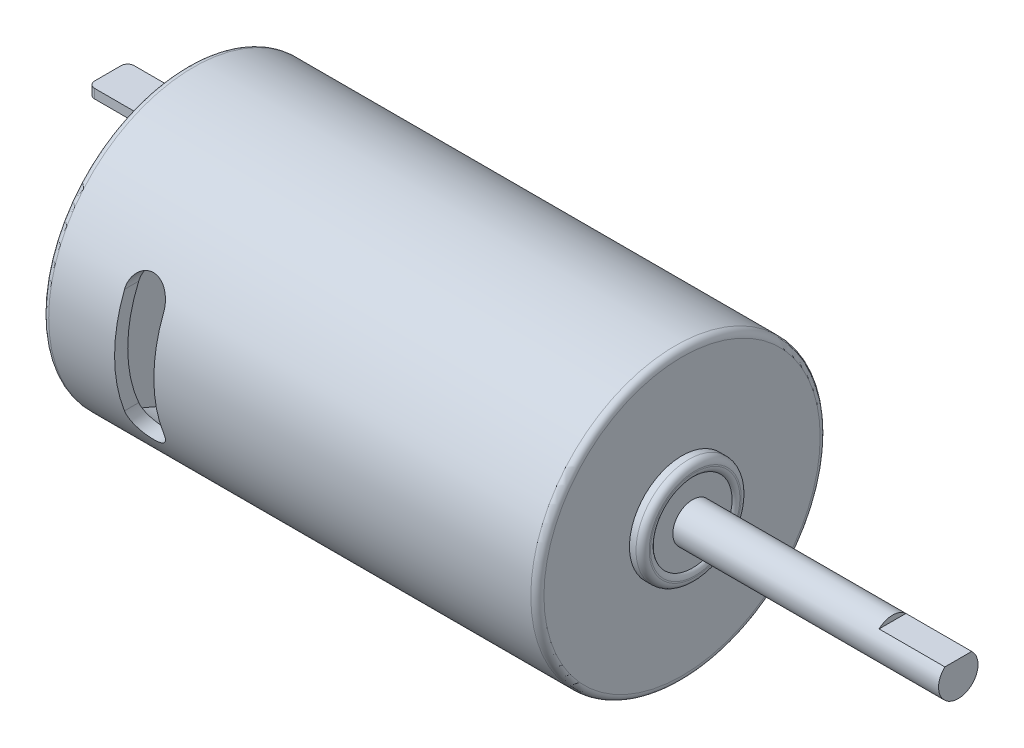
SolidWorks part; units mm, degrees
ref_plane "前视基准面" through (0, 0, 0) normal (0, 0, 1) x (1, 0, 0)
ref_plane "上视基准面" through (0, 0, 0) normal (0, 1, 0) x (1, 0, 0)
ref_plane "右视基准面" through (0, 0, 0) normal (1, 0, 0) x (0, 0, -1)
sketch "草图1" plane through (0, 0, 0) normal (1, 0, 0) x (0, 0, -1)
  circle A0 centre (0, 0) radius 11
  dimension "D1" = 22
extrude "凸台-拉伸1" add sketch "草图1" along normal mid plane 37.65
sketch "草图3" plane through (0, 0, 0) normal (1, 0, 0) x (0, 0, -1)
  circle A0 centre (0, 0) radius 10
  circle A1 centre (0, 0) radius 11 construction
  dimension "D1" = 1
extrude "切除-拉伸1" cut sketch "草图3" against normal mid plane 35.65
sketch "草图4" plane through (0, 0, 0) normal (0, 0, 1) x (1, 0, 0)
  line L0 (-11.825, 4) -> (-11.825, -4) construction
  line L1 (-10.3329, 4) -> (-10.3329, -4)
  line L2 (-13.3171, 4) -> (-13.3171, -4)
  line L3 (18.825, 11) -> (-18.825, 11) construction
  line L4 (-18.825, 11) -> (-18.825, -11) construction
  arc A0 (-10.3329, 4) -> (-13.3171, 4) centre (-11.825, 4) ccw
  arc A1 (-13.3171, -4) -> (-10.3329, -4) centre (-11.825, -4) ccw
  point P2 (-11.825, 0)
  dimension "D1" = 7
  dimension "D2" = 7
extrude "切除-拉伸2" cut sketch "草图4" along normal through all
fillet "圆角1" radius 0.5 2 edges at (18.825, 0, -11) (-18.825, 0, -11)
sketch "草图5" plane through (-18.825, 0, 0) normal (-1, 0, 0) x (0, 0, 1)
  line L0 (-10.5, 0) -> (10.5, 0) construction
  line L1 (-1.5, 6.65) -> (1.5, 6.65)
  line L2 (-1.5, 6.65) -> (-1.5, 7.35)
  line L3 (-1.5, 7.35) -> (1.5, 7.35)
  line L4 (1.5, 6.65) -> (1.5, 7.35)
  line L5 (-1.5, 6.65) -> (1.5, 7.35) construction
  line L6 (-1.5, 7.35) -> (1.5, 6.65) construction
  line L7 (-1.5, -7.35) -> (1.5, -6.65) construction
  line L8 (-1.5, -6.65) -> (1.5, -7.35) construction
  line L9 (1.5, -6.65) -> (1.5, -7.35)
  line L10 (-1.5, -7.35) -> (1.5, -7.35)
  line L11 (-1.5, -6.65) -> (-1.5, -7.35)
  line L12 (-1.5, -6.65) -> (1.5, -6.65)
  circle A0 centre (0, 0) radius 10.5 construction
  point P0 (0, 7)
  point P15 (0, -7)
  dimension "D1" = 0.7
  dimension "D2" = 3
  dimension "D3" = 7
extrude "凸台-拉伸2" add sketch "草图5" along normal blind 6
fillet "圆角2" radius 0.5 4 edges at (-24.825, -7, -1.5) (-24.825, -7, 1.5) (-24.825, 7, -1.5) (-24.825, 7, 1.5)
sketch "草图7" plane through (18.825, 0, 0) normal (1, 0, 0) x (0, 0, -1)
  circle A0 centre (0, 0) radius 3.5
  dimension "D1" = 7
extrude "凸台-拉伸3" add sketch "草图7" along normal blind 1
sketch "草图8" plane through (19.825, 0, 0) normal (1, 0, 0) x (0, 0, -1)
  circle A0 centre (0, 0) radius 1.5
  dimension "D1" = 3
extrude "凸台-拉伸4" add sketch "草图8" along normal blind 20
sketch "草图9" plane through (39.825, 0, 0) normal (1, 0, 0) x (0, 0, -1)
  line L0 (-1.0198, 1.1) -> (1.0198, 1.1)
  circle A0 centre (0, 0) radius 1.5 construction
  arc A1 (1.0198, 1.1) -> (-1.0198, 1.1) centre (0, 0) ccw
  dimension "D1" = 1.1
extrude "切除-拉伸3" cut sketch "草图9" against normal blind 5
sketch "草图10" plane through (18.825, 0, 0) normal (1, 0, 0) x (0, 0, -1)
  circle A0 centre (0, 0) radius 4
  dimension "D1" = 8
extrude "凸台-拉伸5" add sketch "草图10" along normal blind 1
fillet "圆角4" radius 0.5 1 edges at (19.825, 0, -4)
sketch "草图11" plane through (19.825, 0, 0) normal (1, 0, 0) x (0, 0, -1)
  circle A0 centre (0, 0) radius 3
  circle A1 centre (0, 0) radius 1.5
  circle A2 centre (0, 0) radius 3.5 construction
  arc A4 (-1.0198, 1.1) -> (1.0198, 1.1) centre (0, 0) ccw construction
  dimension "D1" = 0.5
extrude "切除-拉伸4" cut sketch "草图11" against normal blind 0.2
fillet "圆角5" radius 0.5 1 edges at (19.825, 0, -3)
